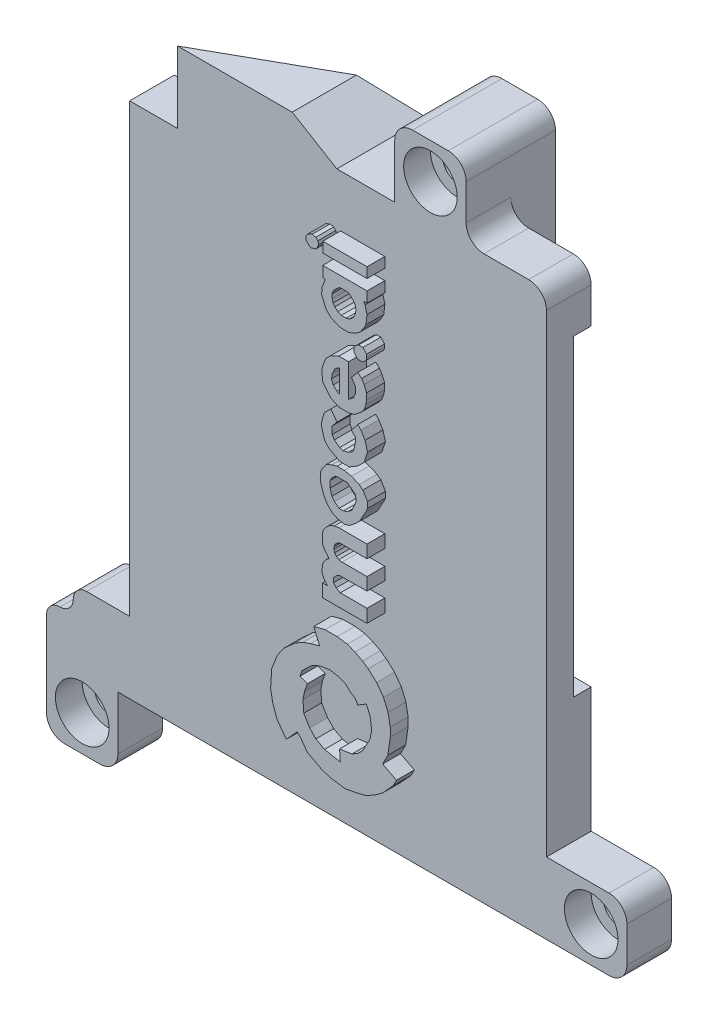
SolidWorks part; units mm, degrees
ref_plane "前视基准面" through (0, 0, 0) normal (0, 0, 1) x (1, 0, 0)
ref_plane "上视基准面" through (0, 0, 0) normal (0, 1, 0) x (1, 0, 0)
ref_plane "右视基准面" through (0, 0, 0) normal (1, 0, 0) x (0, 0, -1)
other "Configuration Table"
sketch "草图1" plane through (0, 0, 0) normal (0, 0, 1) x (1, 0, 0)
  line L0 (-34, -35.5) -> (-34, -27.5)
  line L1 (-34, -27.5) -> (-21.9792, -27.5)
  line L2 (-21.9792, -27.5) -> (-21.9792, 22.5)
  line L3 (-21.9792, 22.5) -> (-6.2665, 22.5)
  line L4 (-6.2665, 22.5) -> (-6.2665, 30.5)
  line L5 (-6.2665, 30.5) -> (-3.4792, 30.5)
  line L6 (-3.4792, 30.5) -> (1.5208, 27.5)
  line L7 (1.5208, 27.5) -> (8, 27.5)
  line L8 (8, 27.5) -> (8, 35.5)
  line L9 (8, 35.5) -> (16, 35.5)
  line L10 (16, 35.5) -> (16, 22.5)
  line L11 (16, 22.5) -> (16, -27.5)
  line L12 (16, -27.5) -> (34, -27.5)
  line L13 (34, -27.5) -> (34, -35.5)
  line L14 (34, -35.5) -> (-34, -35.5)
extrude "凸台-拉伸1" add sketch "草图1" along normal blind 5
sketch "草图2" plane through (0, 0, 5) normal (0, 0, 1) x (1, 0, 0)
  line L0 (12, 35.5) -> (12, 6.2444) construction
  line L1 (16, 35.5) -> (8, 35.5) construction
  line L2 (34, -31.5) -> (-34, -31.5) construction
  line L3 (34, -35.5) -> (34, -27.5) construction
  line L4 (-34, -27.5) -> (-34, -35.5) construction
  circle A0 centre (12, 31.5) radius 1.6
  circle A1 centre (30, -31.5) radius 1.6
  circle A2 centre (-30, -31.5) radius 1.6
  dimension "D2" = 3.2
  dimension "D3" = 3.2
  dimension "D5" = 3.2
  dimension "D1" = 4
  dimension "D4" = 4
  dimension "D6" = 4
extrude "切除-拉伸1" cut sketch "草图2" against normal through all
sketch "草图3" plane through (0, 0, 0) normal (0, 0, -1) x (-1, 0, 0)
  line L0 (-8, 35.5) -> (-8, 27.5)
  line L1 (-16, 35.5) -> (-8, 35.5)
  line L2 (-16, 35.5) -> (-16, 22.5)
  line L3 (-16, 22.5) -> (6.2665, 22.5)
  line L4 (6.2665, 30.5) -> (6.2665, 22.5)
  line L5 (-8, 27.5) -> (-1.5208, 27.5)
  line L6 (-1.5208, 27.5) -> (3.4792, 30.5)
  line L7 (3.4792, 30.5) -> (6.2665, 30.5)
extrude "凸台-拉伸2" add sketch "草图3" along normal blind 5
sketch "草图4" plane through (0, 30.5, 0) normal (0, 1, 0) x (1, 0, 0)
  line L0 (-6.2665, 5) -> (1.5208, 5)
  line L1 (1.5208, 5) -> (-6.2665, 0.6336)
  line L2 (-6.2665, -5) -> (-6.2665, 5) construction
  line L3 (-6.2665, 0.6336) -> (-6.2665, 5)
  dimension "D1" = 29.28
extrude "切除-拉伸2" cut sketch "草图4" against normal through all
sketch "草图5" plane through (0, 0, 5) normal (0, 0, 1) x (1, 0, 0)
  line L1 (-6.2665, 30.5) -> (-21.9792, 30.5)
  line L2 (-6.2665, 30.5) -> (-6.2665, 22.5)
  line L3 (-6.2665, 22.5) -> (-21.9792, 22.5)
  line L4 (-21.9792, 30.5) -> (-21.9792, 22.5)
extrude "凸台-拉伸3" add sketch "草图5" against normal up to vertex (5.6336 mm away) up to point (-6.2665, 22.5, -0.6336)
sketch "草图6" plane through (0, 30.5, 0) normal (0, 1, 0) x (1, 0, 0)
  line L0 (-6.2665, 0.6336) -> (-16.3136, -5)
  line L1 (-3.4792, -5) -> (-21.9792, -5) construction
  line L2 (-16.3136, -5) -> (-21.9792, -5)
  line L3 (-21.9792, -5) -> (-21.9792, 0.6336)
  line L4 (-21.9792, 0.6336) -> (-6.2665, 0.6336)
  line L5 (-6.2665, 0.6336) -> (-3.4792, 2.1964) construction
  dimension "D1" = 180
extrude "切除-拉伸3" cut sketch "草图6" against normal up to vertex (8 mm away) up to point (-6.2665, 22.5, -0.6336)
sketch "草图7" plane through (0, 0, 5) normal (0, 0, 1) x (1, 0, 0)
  line L0 (-21.9792, 22.5) -> (-16.3136, 22.5) construction
  line L1 (-21.9792, -27.5) -> (-21.6792, -27.5)
  line L2 (-21.9792, -27.5) -> (-21.9792, 22.5)
  line L3 (-21.9792, 22.5) -> (-21.6792, 22.5)
  line L4 (-21.6792, -27.5) -> (-21.6792, 22.5)
  dimension "D1" = 0.3
extrude "切除-拉伸4" cut sketch "草图7" against normal through all
sketch "草图8" plane through (0, -27.5, 0) normal (0, 1, 0) x (1, 0, 0)
  line L0 (34, 0) -> (16, 0) construction
  line L1 (16, -5) -> (25, -5)
  line L2 (16, -5) -> (16, 0)
  line L3 (16, 0) -> (25, 0)
  line L4 (25, -5) -> (25, 0)
extrude "凸台-拉伸4" add sketch "草图8" along normal up to vertex (55 mm away) up to point (8, 27.5, 5)
fillet "圆角1" radius 2 8 edges at (16, 35.5, 0) (8, 35.5, 0) (16, 27.5, 2.5) (25, 27.5, 2.5) (34, -27.5, 2.5) (34, -35.5, 2.5) (-34, -27.5, 2.5) (-34, -35.5, 2.5)
sketch "草图9" plane through (0, 0, 5) normal (0, 0, 1) x (1, 0, 0)
  circle A0 centre (12, 31.5) radius 3
  circle A1 centre (30, -31.5) radius 3
  circle A2 centre (-30, -31.5) radius 3
  dimension "D1" = 6
  dimension "D2" = 6
  dimension "D3" = 6
extrude "切除-拉伸5" cut sketch "草图9" against normal blind 3
sketch "草图10" plane through (0, 0, 0) normal (0, 0, 1) x (1, 0, 0)
  circle A0 centre (12, 31.5) radius 1.6
extrude "切除-拉伸6" cut sketch "草图10" against normal through all
sketch "草图11" plane through (0, 0, 5) normal (0, 0, 1) x (1, 0, 0)
  line L0 (-21.6792, -27.5) -> (-32, -27.5) construction
  line L1 (-26, -27.5) -> (-34, -27.5)
  line L2 (-26, -27.5) -> (-26, -35.5)
  line L3 (-26, -35.5) -> (-34, -35.5)
  line L4 (-34, -27.5) -> (-34, -35.5)
  line L5 (-34, -29.5) -> (-34, -33.5) construction
  dimension "D1" = 0
  dimension "D2" = 8
  dimension "D3" = 8
extrude "切除-拉伸7" cut sketch "草图11" against normal through all
sketch "草图12" plane through (0, 0, 5) normal (0, 0, 1) x (1, 0, 0)
  line L1 (-26, -27.5) -> (-31, -27.5)
  line L2 (-26, -27.5) -> (-26, -35.5)
  line L4 (-31, -27.5) -> (-31, -35.5)
  line L5 (-31, -35.5) -> (-23, -43.5) construction
  line L6 (-26, -35.5) -> (-23, -35.5)
  line L7 (-31, -35.5) -> (-31, -43.5)
  line L8 (-31, -43.5) -> (-23, -43.5)
  line L9 (-23, -35.5) -> (-23, -43.5)
  circle A0 centre (-27, -39.5) radius 1.6
  dimension "D5" = 3.2
  dimension "D1" = 5
  dimension "D3" = 8
  dimension "D4" = 8
extrude "凸台-拉伸5" add sketch "草图12" against normal up to surface (5 mm away) up to face at (10.2049, -4.4333, 0)
sketch "草图13" plane through (0, 0, 5) normal (0, 0, 1) x (1, 0, 0)
  circle A0 centre (-27, -39.5) radius 3
  dimension "D1" = 6
extrude "切除-拉伸8" cut sketch "草图13" against normal blind 3
fillet "圆角2" radius 2 3 edges at (-23, -43.5, 2.5) (-31, -43.5, 2.5) (-31, -27.5, 2.5)
sketch "草图14" plane through (0, 0, 5) normal (0, 0, 1) x (1, 0, 0)
  line L0 (-31, -29.5) -> (-31, -41.5) construction
  line L1 (-28, -30.5) -> (-36.8602, -30.5)
  line L2 (-28, -30.5) -> (-28, -21.3319)
  line L3 (-28, -21.3319) -> (-36.8602, -21.3319)
  line L4 (-36.8602, -30.5) -> (-36.8602, -21.3319)
  line L5 (-21.6792, -27.5) -> (-29, -27.5) construction
  dimension "D1" = 3
  dimension "D2" = 3
extrude "切除-拉伸9" cut sketch "草图14" against normal through all
fillet "圆角3" radius 1.5 3 edges at (-28, -27.5, 2.5) (-28, -30.5, 2.5) (-31, -30.5, 2.5)
sketch "草图17" plane through (0, 0, 5) normal (0, 0, 1) x (1, 0, 0)
  line L0 (-123.1602, 102.4797) -> (-123.1602, 641.1464) construction
  line L61 (1.9167, -12.8933) -> (6.8963, -12.8933)
  line L62 (6.8963, -12.8933) -> (6.8963, -11.4257)
  line L63 (6.8963, -11.4257) -> (3.9086, -11.4257)
  line L64 (3.9086, -11.4257) -> (3.4368, -11.1811)
  line L65 (3.4368, -11.1811) -> (3.1573, -10.8141)
  line L66 (3.1573, -10.8141) -> (3.1573, -10.3074)
  line L67 (3.1573, -10.3074) -> (3.4019, -10.0628)
  line L68 (3.4019, -10.0628) -> (3.6092, -9.8555)
  line L69 (3.6092, -9.8555) -> (3.8561, -9.7878)
  line L70 (3.8561, -9.7878) -> (6.8963, -9.7605)
  line L71 (6.8963, -9.7605) -> (6.8963, -8.3521)
  line L72 (6.8963, -8.3521) -> (4.0976, -8.3521)
  line L73 (4.0976, -8.3521) -> (3.7327, -8.2974)
  line L74 (3.7327, -8.2974) -> (3.4687, -8.1242)
  line L75 (3.4687, -8.1242) -> (3.2796, -7.8462)
  line L76 (3.2796, -7.8462) -> (3.1963, -7.5425)
  line L77 (3.1963, -7.5425) -> (3.1963, -7.2992)
  line L78 (3.1963, -7.2992) -> (3.3274, -7.0029)
  line L79 (3.3274, -7.0029) -> (3.5484, -6.7819)
  line L80 (3.5484, -6.7819) -> (3.8277, -6.6293)
  line L81 (3.8277, -6.6293) -> (4.2706, -6.6293)
  line L82 (4.2706, -6.6293) -> (6.8963, -6.6293)
  line L83 (6.8963, -6.6293) -> (6.8963, -5.1964)
  line L84 (6.8963, -5.1964) -> (3.7637, -5.1964)
  line L85 (3.7637, -5.1964) -> (3.2619, -5.2515)
  line L86 (3.2619, -5.2515) -> (2.7705, -5.4686)
  line L87 (2.7705, -5.4686) -> (2.4719, -5.7053)
  line L88 (2.4719, -5.7053) -> (2.2087, -5.9685)
  line L89 (2.2087, -5.9685) -> (2.0375, -6.2295)
  line L90 (2.0375, -6.2295) -> (1.9167, -6.5984)
  line L91 (1.9167, -6.5984) -> (1.9167, -7.6457)
  line L92 (1.9167, -7.6457) -> (2.0876, -8.0326)
  line L93 (2.0876, -8.0326) -> (2.3192, -8.3247)
  line L94 (2.3192, -8.3247) -> (2.5525, -8.619)
  line L95 (2.5525, -8.619) -> (2.6441, -8.7346)
  line L96 (2.6441, -8.7346) -> (2.3192, -8.9921)
  line L97 (2.3192, -8.9921) -> (2.0876, -9.2918)
  line L98 (2.0876, -9.2918) -> (1.9504, -9.602)
  line L99 (1.9504, -9.602) -> (1.8814, -10.0628)
  line L100 (1.8814, -10.0628) -> (1.8814, -10.5436)
  line L101 (1.8814, -10.5436) -> (1.9928, -10.7958)
  line L102 (1.9928, -10.7958) -> (2.1367, -11.0592)
  line L103 (2.1367, -11.0592) -> (2.3192, -11.2895)
  line L104 (2.3192, -11.2895) -> (2.4816, -11.4519)
  line L105 (2.4816, -11.4519) -> (1.9371, -11.4519)
  line L106 (1.9371, -11.4519) -> (1.9167, -12.8933)
  line L107 (3.2619, -0.4529) -> (2.8925, -0.8223)
  line L108 (2.8925, -0.8223) -> (2.7705, -1.0981)
  line L109 (2.7705, -1.0981) -> (2.7705, -1.8309)
  line L110 (2.7705, -1.8309) -> (2.963, -2.533)
  line L111 (2.963, -2.533) -> (3.2619, -2.9101)
  line L112 (3.2619, -2.9101) -> (3.7637, -3.2978)
  line L113 (3.7637, -3.2978) -> (4.2706, -3.2978)
  line L114 (4.2706, -3.2978) -> (4.6855, -3.1841)
  line L115 (4.6855, -3.1841) -> (5.2088, -2.7693)
  line L116 (5.2088, -2.7693) -> (5.4686, -2.182)
  line L117 (5.4686, -2.182) -> (5.6742, -1.7171)
  line L118 (5.6742, -1.7171) -> (5.6014, -1.0551)
  line L119 (5.6014, -1.0551) -> (5.16, -0.7141)
  line L120 (5.16, -0.7141) -> (4.6855, -0.3474)
  line L121 (4.6855, -0.3474) -> (4.0491, -0.3474)
  line L122 (4.0491, -0.3474) -> (3.4379, -0.3474)
  line L123 (3.4379, -0.3474) -> (3.2619, -0.4529)
  line L124 (1.6895, -1.3861) -> (1.6895, -0.8223)
  line L125 (1.6895, -0.8223) -> (1.9167, -0.3086)
  line L126 (1.9167, -0.3086) -> (2.3403, 0.2396)
  line L127 (2.3403, 0.2396) -> (2.963, 0.5147)
  line L128 (2.963, 0.5147) -> (3.5484, 0.6751)
  line L129 (3.5484, 0.6751) -> (4.3673, 0.6751)
  line L130 (4.3673, 0.6751) -> (5.16, 0.5147)
  line L131 (5.16, 0.5147) -> (5.6014, 0.3195)
  line L132 (5.6014, 0.3195) -> (6.0161, 0.136)
  line L133 (6.0161, 0.136) -> (6.4361, -0.1884)
  line L134 (6.4361, -0.1884) -> (6.7053, -0.6376)
  line L135 (6.7053, -0.6376) -> (6.9556, -1.0551)
  line L136 (6.9556, -1.0551) -> (6.9556, -1.7171)
  line L137 (6.9556, -1.7171) -> (6.7753, -2.1246)
  line L138 (6.7753, -2.1246) -> (6.2961, -2.9767)
  line L139 (6.2961, -2.9767) -> (6.0518, -3.4111)
  line L140 (6.0518, -3.4111) -> (5.6742, -3.7888)
  line L141 (5.6742, -3.7888) -> (4.9227, -4.3844)
  line L142 (4.9227, -4.3844) -> (4.3673, -4.5366)
  line L143 (4.3673, -4.5366) -> (3.5748, -4.3762)
  line L144 (3.5748, -4.3762) -> (3.0162, -4.1292)
  line L145 (3.0162, -4.1292) -> (2.4719, -3.5849)
  line L146 (2.4719, -3.5849) -> (2.0375, -2.8602)
  line L147 (2.0375, -2.8602) -> (1.8031, -2.1246)
  line L148 (1.8031, -2.1246) -> (1.6532, -1.5776)
  line L149 (1.6532, -1.5776) -> (1.6895, -1.3861)
  line L150 (3.5484, 4.9618) -> (2.8315, 5.8662)
  line L151 (2.8315, 5.8662) -> (2.1285, 5.1632)
  line L152 (2.1285, 5.1632) -> (1.9167, 4.5162)
  line L153 (1.9167, 4.5162) -> (1.7771, 3.7802)
  line L154 (1.7771, 3.7802) -> (1.984, 3.0251)
  line L155 (1.984, 3.0251) -> (2.1733, 2.4311)
  line L156 (2.1733, 2.4311) -> (2.6516, 1.9528)
  line L157 (2.6516, 1.9528) -> (3.8277, 1.2913)
  line L158 (3.8277, 1.2913) -> (4.9227, 1.2913)
  line L159 (4.9227, 1.2913) -> (5.863, 1.8549)
  line L160 (5.863, 1.8549) -> (6.5707, 2.5627)
  line L161 (6.5707, 2.5627) -> (6.7832, 3.2119)
  line L162 (6.7832, 3.2119) -> (6.9556, 3.7383)
  line L163 (6.9556, 3.7383) -> (6.677, 4.7549)
  line L164 (6.677, 4.7549) -> (6.2168, 5.5226)
  line L165 (6.2168, 5.5226) -> (5.863, 5.8764)
  line L166 (5.863, 5.8764) -> (5.1563, 4.9618)
  line L167 (5.1563, 4.9618) -> (5.6019, 4.5162)
  line L168 (5.6019, 4.5162) -> (5.6019, 4.1105)
  line L169 (5.6019, 4.1105) -> (5.4676, 3.4026)
  line L170 (5.4676, 3.4026) -> (5.326, 2.9701)
  line L171 (5.326, 2.9701) -> (4.8297, 2.6726)
  line L172 (4.8297, 2.6726) -> (4.1985, 2.4996)
  line L173 (4.1985, 2.4996) -> (3.8277, 2.621)
  line L174 (3.8277, 2.621) -> (3.2397, 3.0753)
  line L175 (3.2397, 3.0753) -> (2.9979, 3.4786)
  line L176 (2.9979, 3.4786) -> (2.9979, 4.3133)
  line L177 (2.9979, 4.3133) -> (3.5484, 4.9618)
  line L178 (5.1563, 10.0959) -> (5.863, 10.9283)
  line L179 (5.863, 10.9283) -> (6.2961, 10.5606)
  line L180 (6.2961, 10.5606) -> (6.5707, 10.1024)
  line L181 (6.5707, 10.1024) -> (6.863, 9.4408)
  line L182 (6.863, 9.4408) -> (6.863, 8.7708)
  line L183 (6.863, 8.7708) -> (6.7636, 8.247)
  line L184 (6.7636, 8.247) -> (6.5707, 7.6577)
  line L185 (6.5707, 7.6577) -> (6.2168, 7.2409)
  line L186 (6.2168, 7.2409) -> (5.5096, 6.6802)
  line L187 (5.5096, 6.6802) -> (4.8297, 6.4939)
  line L188 (4.8297, 6.4939) -> (3.8277, 6.4939)
  line L189 (3.8277, 6.4939) -> (2.8315, 6.9344)
  line L190 (2.8315, 6.9344) -> (2.3653, 7.5225)
  line L191 (2.3653, 7.5225) -> (1.9412, 8.0575)
  line L192 (1.9412, 8.0575) -> (1.8627, 8.7708)
  line L193 (1.8627, 8.7708) -> (1.8627, 9.3543)
  line L194 (1.8627, 9.3543) -> (2.067, 9.9782)
  line L195 (2.067, 9.9782) -> (2.3031, 10.5121)
  line L196 (2.3031, 10.5121) -> (2.8315, 11.0405)
  line L197 (2.8315, 11.0405) -> (3.19, 11.1989)
  line L198 (3.19, 11.1989) -> (3.7435, 11.4434)
  line L199 (3.7435, 11.4434) -> (4.3752, 11.4434)
  line L200 (4.3752, 11.4434) -> (4.8297, 11.4434)
  line L201 (4.8297, 11.4434) -> (4.8297, 7.79)
  line L202 (4.8297, 7.79) -> (5.3791, 8.2256)
  line L203 (5.3791, 8.2256) -> (5.6019, 8.7294)
  line L204 (5.6019, 8.7294) -> (5.6019, 9.4408)
  line L205 (5.6019, 9.4408) -> (5.1563, 10.0959)
  line L206 (3.8277, 10.3315) -> (3.8277, 7.79)
  line L207 (3.8277, 7.79) -> (3.5484, 7.9135)
  line L208 (3.5484, 7.9135) -> (3.1188, 8.3432)
  line L209 (3.1188, 8.3432) -> (2.9068, 8.823)
  line L210 (2.9068, 8.823) -> (3.0128, 9.3818)
  line L211 (3.0128, 9.3818) -> (3.2513, 9.9212)
  line L212 (3.2513, 9.9212) -> (3.5484, 10.2183)
  line L213 (3.5484, 10.2183) -> (3.8277, 10.3315)
  line L214 (6.1739, 13.6374) -> (6.4334, 13.6374)
  line L215 (6.4334, 13.6374) -> (6.6021, 13.4687)
  line L216 (6.6021, 13.4687) -> (6.863, 13.2078)
  line L217 (6.863, 13.2078) -> (6.863, 12.8771)
  line L218 (6.863, 12.8771) -> (6.8053, 12.573)
  line L219 (6.8053, 12.573) -> (6.6021, 12.3697)
  line L220 (6.6021, 12.3697) -> (6.3507, 12.1987)
  line L221 (6.3507, 12.1987) -> (5.863, 12.2056)
  line L222 (5.863, 12.2056) -> (5.6378, 12.4308)
  line L223 (5.6378, 12.4308) -> (5.4376, 12.725)
  line L224 (5.4376, 12.725) -> (5.4376, 13.2078)
  line L225 (5.4376, 13.2078) -> (5.682, 13.4522)
  line L226 (5.682, 13.4522) -> (5.9543, 13.6374)
  line L227 (5.9543, 13.6374) -> (6.1739, 13.6374)
  line L228 (3.19, 17.5648) -> (3.5689, 17.9437)
  line L229 (3.5689, 17.9437) -> (3.8096, 18.1346)
  line L230 (3.8096, 18.1346) -> (4.0594, 18.162)
  line L231 (4.0594, 18.162) -> (4.4421, 18.162)
  line L232 (4.4421, 18.162) -> (4.7401, 18.162)
  line L233 (4.7401, 18.162) -> (5.0508, 17.9582)
  line L234 (5.0508, 17.9582) -> (5.2985, 17.7105)
  line L235 (5.2985, 17.7105) -> (5.5096, 17.4441)
  line L236 (5.5096, 17.4441) -> (5.6172, 17.1788)
  line L237 (5.6172, 17.1788) -> (5.6532, 16.8514)
  line L238 (5.6532, 16.8514) -> (5.6009, 16.5023)
  line L239 (5.6009, 16.5023) -> (5.404, 16.0571)
  line L240 (5.404, 16.0571) -> (5.1209, 15.774)
  line L241 (5.1209, 15.774) -> (4.8954, 15.6206)
  line L242 (4.8954, 15.6206) -> (4.5627, 15.5294)
  line L243 (4.5627, 15.5294) -> (4.0131, 15.5372)
  line L244 (4.0131, 15.5372) -> (3.6267, 15.708)
  line L245 (3.6267, 15.708) -> (3.2865, 15.9969)
  line L246 (3.2865, 15.9969) -> (3.0941, 16.2797)
  line L247 (3.0941, 16.2797) -> (2.9979, 16.6309)
  line L248 (2.9979, 16.6309) -> (2.9487, 17.0782)
  line L249 (2.9487, 17.0782) -> (3.0772, 17.3687)
  line L250 (3.0772, 17.3687) -> (3.19, 17.5648)
  line L251 (1.9412, 19.3527) -> (6.8963, 19.3527)
  line L252 (6.8963, 19.3527) -> (6.8963, 18.162)
  line L253 (6.8963, 18.162) -> (6.5153, 18.162)
  line L254 (6.5153, 18.162) -> (6.677, 17.892)
  line L255 (6.677, 17.892) -> (6.7636, 17.5648)
  line L256 (6.7636, 17.5648) -> (6.8963, 17.0639)
  line L257 (6.8963, 17.0639) -> (6.83, 16.5023)
  line L258 (6.83, 16.5023) -> (6.7703, 15.9969)
  line L259 (6.7703, 15.9969) -> (6.5153, 15.5294)
  line L260 (6.5153, 15.5294) -> (6.1137, 14.9704)
  line L261 (6.1137, 14.9704) -> (5.682, 14.6423)
  line L262 (5.682, 14.6423) -> (5.2985, 14.4812)
  line L263 (5.2985, 14.4812) -> (4.8617, 14.2979)
  line L264 (4.8617, 14.2979) -> (4.0976, 14.2979)
  line L265 (4.0976, 14.2979) -> (3.6267, 14.3896)
  line L266 (3.6267, 14.3896) -> (2.8315, 14.7573)
  line L267 (2.8315, 14.7573) -> (2.3031, 15.3093)
  line L268 (2.3031, 15.3093) -> (2.108, 15.774)
  line L269 (2.108, 15.774) -> (1.8138, 16.4748)
  line L270 (1.8138, 16.4748) -> (1.8627, 17.2356)
  line L271 (1.8627, 17.2356) -> (2.067, 17.7105)
  line L272 (2.067, 17.7105) -> (2.2494, 18.1346)
  line L273 (2.2494, 18.1346) -> (1.9649, 18.1346)
  line L274 (1.9649, 18.1346) -> (1.9412, 19.3527)
  line L275 (0.7537, 21.7761) -> (1.1657, 21.6959)
  line L276 (1.1657, 21.6959) -> (1.3924, 21.459)
  line L277 (1.3924, 21.459) -> (1.4823, 21.1199)
  line L278 (1.4823, 21.1199) -> (1.3438, 20.798)
  line L279 (1.3438, 20.798) -> (1.1657, 20.5501)
  line L280 (1.1657, 20.5501) -> (0.9305, 20.4878)
  line L281 (0.9305, 20.4878) -> (0.5832, 20.3958)
  line L282 (0.5832, 20.3958) -> (0.3684, 20.5501)
  line L283 (0.3684, 20.5501) -> (0.0804, 20.8509)
  line L284 (0.0804, 20.8509) -> (0.0804, 21.2894)
  line L285 (0.0804, 21.2894) -> (0.2873, 21.5774)
  line L286 (0.2873, 21.5774) -> (0.5185, 21.6745)
  line L287 (0.5185, 21.6745) -> (0.7537, 21.7761)
  line L288 (1.9412, 21.6959) -> (1.9412, 20.5501)
  line L289 (1.9412, 20.5501) -> (6.8963, 20.5501)
  line L290 (6.8963, 20.5501) -> (6.8963, 21.6959)
  line L291 (6.8963, 21.6959) -> (1.9412, 21.6959)
  line L292 (-0.6167, -21.7774) -> (0.2244, -22.0822)
  line L293 (0.2244, -22.0822) -> (-0.0982, -22.9725)
  line L294 (-0.0982, -22.9725) -> (-0.2707, -23.8585)
  line L295 (-0.2707, -23.8585) -> (-0.1845, -25.1401)
  line L296 (-0.1845, -25.1401) -> (0.4758, -26.2428)
  line L297 (0.4758, -26.2428) -> (1.1657, -26.9635)
  line L298 (1.1657, -26.9635) -> (2.1367, -27.4932)
  line L299 (2.1367, -27.4932) -> (2.963, -27.6541)
  line L300 (2.963, -27.6541) -> (3.9086, -27.8382)
  line L301 (3.9086, -27.8382) -> (3.8254, -26.6032)
  line L302 (3.8254, -26.6032) -> (5.2088, -26.4055)
  line L303 (5.2088, -26.4055) -> (5.863, -26.0138)
  line L304 (5.863, -26.0138) -> (6.4025, -25.4973)
  line L305 (6.4025, -25.4973) -> (6.7967, -24.7747)
  line L306 (6.7967, -24.7747) -> (7.2204, -23.9981)
  line L307 (7.2204, -23.9981) -> (7.4201, -22.9725)
  line L308 (7.4201, -22.9725) -> (7.2411, -21.7206)
  line L309 (7.2411, -21.7206) -> (6.8241, -20.7552)
  line L310 (6.8241, -20.7552) -> (5.863, -21.3307)
  line L311 (5.863, -21.3307) -> (5.5359, -20.7845)
  line L312 (5.5359, -20.7845) -> (5.0305, -20.5088)
  line L313 (5.0305, -20.5088) -> (4.4685, -19.9216)
  line L314 (4.4685, -19.9216) -> (3.8254, -19.6886)
  line L315 (3.8254, -19.6886) -> (2.7705, -19.4832)
  line L316 (2.7705, -19.4832) -> (1.6512, -19.6432)
  line L317 (1.6512, -19.6432) -> (0.7568, -20.0294)
  line L318 (0.7568, -20.0294) -> (0.2244, -20.5391)
  line L319 (0.2244, -20.5391) -> (-0.3764, -21.1142)
  line L320 (-0.3764, -21.1142) -> (-0.6167, -21.7774)
  line L321 (1.5882, -17.7338) -> (0.9305, -16.1737)
  line L322 (0.9305, -16.1737) -> (2.2087, -15.8495)
  line L323 (2.2087, -15.8495) -> (3.5484, -15.8495)
  line L324 (3.5484, -15.8495) -> (4.6855, -16.0116)
  line L325 (4.6855, -16.0116) -> (5.5359, -16.3459)
  line L326 (5.5359, -16.3459) -> (6.4025, -16.7917)
  line L327 (6.4025, -16.7917) -> (7.0284, -17.2273)
  line L328 (7.0284, -17.2273) -> (7.9706, -18.0884)
  line L329 (7.9706, -18.0884) -> (8.7405, -19.1319)
  line L330 (8.7405, -19.1319) -> (9.2474, -20.3341)
  line L331 (9.2474, -20.3341) -> (9.5003, -21.6544)
  line L332 (9.5003, -21.6544) -> (9.5003, -22.6095)
  line L333 (9.5003, -22.6095) -> (9.3914, -23.3737)
  line L334 (9.3914, -23.3737) -> (9.2275, -24.5237)
  line L335 (9.2275, -24.5237) -> (8.6441, -25.658)
  line L336 (8.6441, -25.658) -> (10.1946, -26.4555)
  line L337 (10.1946, -26.4555) -> (9.8267, -27.1707)
  line L338 (9.8267, -27.1707) -> (9.2889, -27.7591)
  line L339 (9.2889, -27.7591) -> (8.6441, -28.4646)
  line L340 (8.6441, -28.4646) -> (7.8975, -29.0155)
  line L341 (7.8975, -29.0155) -> (6.7967, -29.6478)
  line L342 (6.7967, -29.6478) -> (5.863, -29.8846)
  line L343 (5.863, -29.8846) -> (4.4685, -30.1518)
  line L344 (4.4685, -30.1518) -> (2.963, -29.9372)
  line L345 (2.963, -29.9372) -> (1.9167, -29.6478)
  line L346 (1.9167, -29.6478) -> (0.2244, -28.7401)
  line L347 (0.2244, -28.7401) -> (-0.5769, -27.6541)
  line L348 (-0.5769, -27.6541) -> (-0.9318, -27.3297)
  line L349 (-0.9318, -27.3297) -> (-2.1406, -28.6522)
  line L350 (-2.1406, -28.6522) -> (-3.1719, -27.2544)
  line L351 (-3.1719, -27.2544) -> (-3.654, -25.8979)
  line L352 (-3.654, -25.8979) -> (-3.8993, -24.6175)
  line L353 (-3.8993, -24.6175) -> (-3.7766, -22.6095)
  line L354 (-3.7766, -22.6095) -> (-3.1503, -21.0163)
  line L355 (-3.1503, -21.0163) -> (-2.4201, -19.9671)
  line L356 (-2.4201, -19.9671) -> (-1.6508, -19.2662)
  line L357 (-1.6508, -19.2662) -> (-1.1806, -18.8377)
  line L358 (-1.1806, -18.8377) -> (-0.2707, -18.3151)
  line L359 (-0.2707, -18.3151) -> (0.5832, -18.0117)
  line L360 (0.5832, -18.0117) -> (1.5882, -17.7338)
extrude "凸台-拉伸6" add sketch "草图17" along normal blind 2
sketch "草图18" plane through (25, 0, 0) normal (1, 0, 0) x (0, 0, -1)
  line L0 (0, 25.5) -> (0, -27.5) construction
  line L1 (0, -13.5) -> (-2, -13.5)
  line L2 (0, -13.5) -> (0, 21.5)
  line L3 (0, 21.5) -> (-2, 21.5)
  line L4 (-2, -13.5) -> (-2, 21.5)
  line L5 (-5, -27.5) -> (0, -27.5) construction
  line L7 (0, 25.5) -> (-5, 25.5) construction
  dimension "D1" = 14
  dimension "D2" = 4
  dimension "D3" = 2
extrude "切除-拉伸10" cut sketch "草图18" against normal through all
